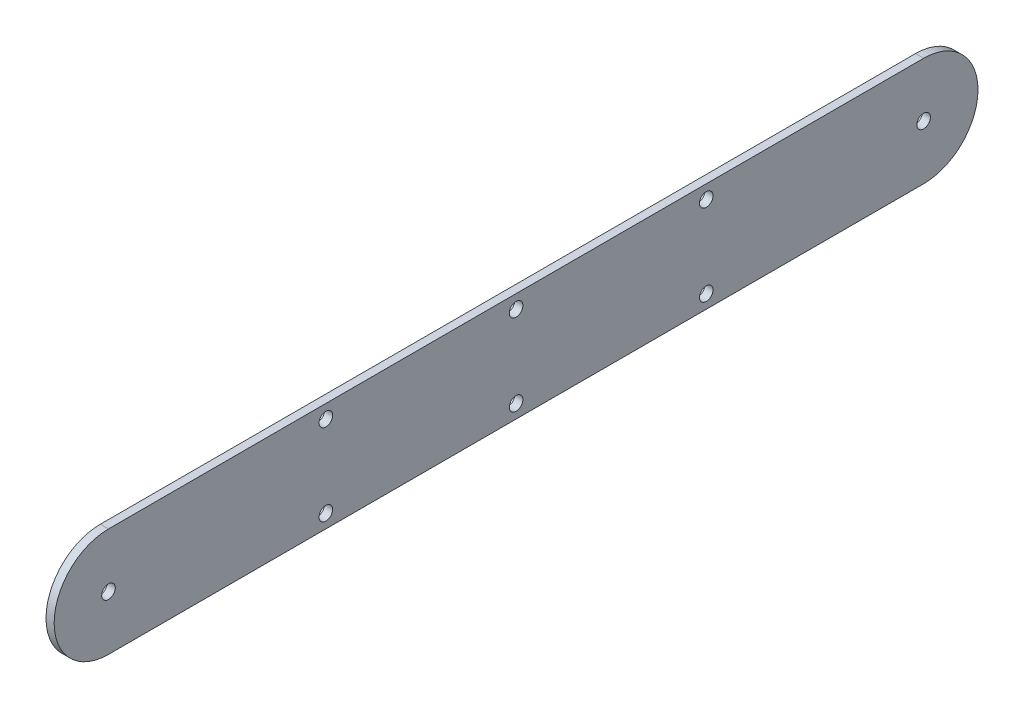
SolidWorks part; units mm, degrees
ref_plane "Front Plane" through (0, 0, 0) normal (0, 0, 1) x (1, 0, 0)
ref_plane "Top Plane" through (0, 0, 0) normal (0, 1, 0) x (1, 0, 0)
ref_plane "Right Plane" through (0, 0, 0) normal (1, 0, 0) x (0, 0, -1)
sketch "Sketch1" plane through (0, 0, 0) normal (1, 0, 0) x (0, 0, -1)
  line L0 (150, 0) -> (-150, 0) construction
  line L1 (-150, -20) -> (150, -20)
  line L2 (-70, 15) -> (243.3324, 15) construction
  line L3 (-150, 20) -> (150, 20)
  line L4 (-70, -15) -> (230.8275, -15) construction
  line L5 (-150, -20) -> (150, 20) construction
  line L6 (-150, 20) -> (150, -20) construction
  arc A0 (150, 20) -> (150, -20) centre (150, 0) cw
  arc A1 (-150, 20) -> (-150, -20) centre (-150, 0) ccw
  circle A2 centre (150, 0) radius 2.5
  circle A3 centre (-150, 0) radius 2.5
  circle A4 centre (70, 15) radius 2.5
  circle A5 centre (70, -15) radius 2.5
  circle A6 centre (-70, 15) radius 2.5
  circle A7 centre (-70, -15) radius 2.5
  circle A8 centre (0, 15) radius 2.5
  circle A9 centre (0, -15) radius 2.5
  point P0 (0, 0)
  dimension "D3" = 5
  dimension "D4" = 5
  dimension "D7" = 5
  dimension "D8" = 5
  dimension "D15" = 5
  dimension "D16" = 5
  dimension "D17" = 5
  dimension "D18" = 5
  dimension "D1" = 300
  dimension "D2" = 40
  dimension "D5" = 80
  dimension "D6" = 0
  dimension "D11" = 80
  dimension "D12" = 0
  dimension "D13" = 30
  dimension "D14" = 15
extrude "Boss-Extrude1" add sketch "Sketch1" along normal blind 3
sketch "Sketch2" plane through (3, 0, 0) normal (1, 0, 0) x (0, 0, -1)
